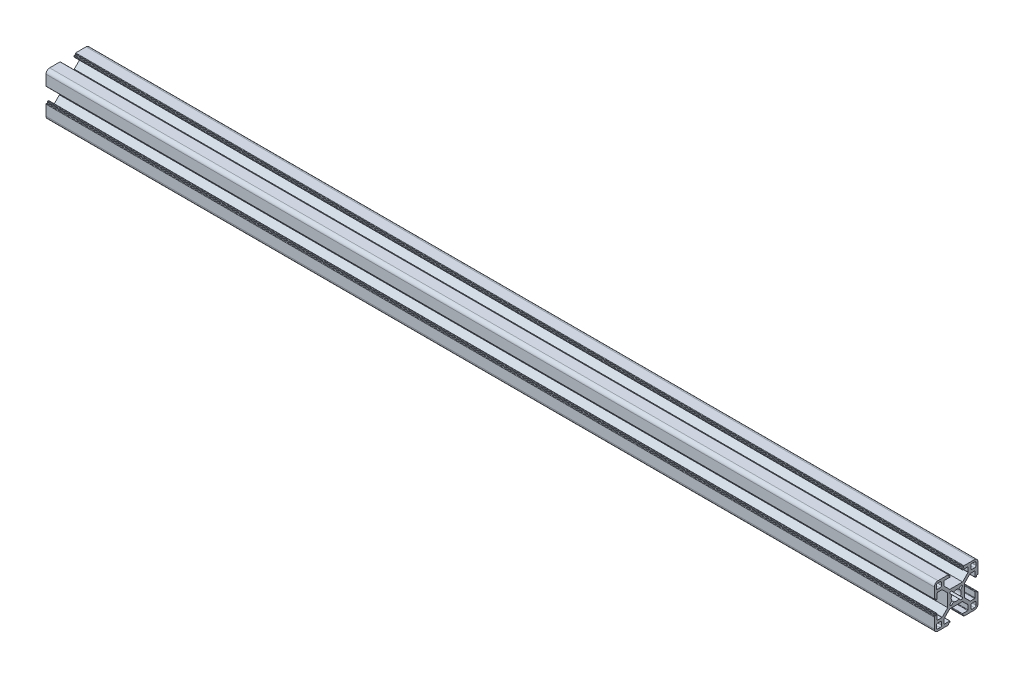
SolidWorks part; units mm, degrees
material "2.0572 (CuZn40Mn2Fe1)"
ref_plane "Front Plane" through (0, 0, 0) normal (0, 0, 1) x (1, 0, 0)
ref_plane "Top Plane" through (0, 0, 0) normal (0, 1, 0) x (1, 0, 0)
ref_plane "Right Plane" through (0, 0, 0) normal (1, 0, 0) x (0, 0, -1)
ref_axis "Axis_X" through (-58.3, 0, 0) along (1, 0, 0)
ref_axis "Axis_Y" through (0, 38.5, 0) along (0, -1, 0)
ref_axis "Axis_Z" through (0, 0, -4.5) along (0, 0, 1)
sketch "Sketch2" plane through (0, 0, 0) normal (1, 0, 0) x (0, 0, -1)
  line L1 (-15, 15) -> (15, 15)
  line L2 (-15, 15) -> (-15, -15)
  line L3 (-15, -15) -> (15, -15)
  line L4 (15, 15) -> (15, -15)
  line L5 (-15, 15) -> (15, -15) construction
  line L6 (-15, -15) -> (15, 15) construction
  point P0 (0, 0)
  dimension "D1" = 30
  dimension "D2" = 30
extrude "Boss-Extrude1" add sketch "Sketch2" along normal blind 610
sketch "Sketch5" plane through (610, 0, 0) normal (1, 0, 0) x (0, 0, -1)
  circle A0 centre (0, 0) radius 3.4
  dimension "D1" = 6.8
extrude "Cut-Extrude2" cut sketch "Sketch5" against normal through all
sketch "Sketch4" plane through (610, 0, 0) normal (1, 0, 0) x (0, 0, -1)
  line L0 (-4.3858, -5.8) -> (4.3858, -5.8)
  line L1 (4.3858, -5.8) -> (8.1621, -9.5763)
  line L2 (8.25, -9.7885) -> (8.25, -13)
  line L3 (8.25, -13) -> (4.1, -13)
  line L4 (4.1, -13) -> (4.1, -14)
  line L5 (4.1, -14) -> (5.1, -14)
  line L6 (5.1, -14) -> (5.1, -15)
  line L7 (-15, -15) -> (15, -15) construction
  line L8 (5.1, -15) -> (-5.1, -15)
  line L9 (-5.1, -15) -> (-5.1, -14)
  line L10 (-5.1, -14) -> (-4.1, -14)
  line L11 (-4.1, -14) -> (-4.1, -13)
  line L12 (-4.1, -13) -> (-8.25, -13)
  line L13 (-8.25, -13) -> (-8.25, -9.7885)
  line L14 (-8.1621, -9.5763) -> (-4.3858, -5.8)
  line L16 (-4.1, -13) -> (4.1, -13) construction
  line L17 (0, -14) -> (0, -15) construction
  line L18 (-4.1, -14) -> (4.1, -14) construction
  line L19 (0, -5.8) -> (0, -13) construction
  line L20 (0, -13) -> (0, -14) construction
  line L21 (15, -15) -> (15, 15) construction
  line L22 (11.05, -10.05) -> (12.65, -10.05)
  line L23 (10.05, -11.05) -> (10.05, -12.65)
  line L24 (11.05, -13.65) -> (12.65, -13.65)
  line L25 (13.65, -11.05) -> (13.65, -12.65)
  line L26 (10.05, -10.05) -> (13.65, -13.65) construction
  line L27 (10.05, -13.65) -> (13.65, -10.05) construction
  line L28 (0, 0) -> (3.5355, -3.5355) construction
  line L29 (15, -15) -> (15, 15) construction
  line L30 (4.0659, -3.0052) -> (2.8753, -1.8146)
  line L31 (3.0052, -4.0659) -> (1.8146, -2.8753)
  arc A0 (12.65, -13.65) -> (13.65, -12.65) centre (12.65, -12.65) ccw
  arc A1 (11.05, -13.65) -> (10.05, -12.65) centre (11.05, -12.65) cw
  arc A2 (10.05, -11.05) -> (11.05, -10.05) centre (11.05, -11.05) cw
  arc A3 (12.65, -10.05) -> (13.65, -11.05) centre (12.65, -11.05) cw
  arc A4 (3.0052, -4.0659) -> (4.0659, -3.0052) centre (3.5355, -3.5355) ccw
  circle A5 centre (0, 0) radius 3.4 construction
  arc A6 (1.8146, -2.8753) -> (2.8753, -1.8146) centre (0, 0) ccw
  arc A7 (-8.25, -9.7885) -> (-8.1621, -9.5763) centre (-7.95, -9.7885) cw
  arc A8 (8.25, -9.7885) -> (8.1621, -9.5763) centre (7.95, -9.7885) ccw
  point P18 (11.85, -11.85)
  point P47 (-8.25, -9.6642)
  point P55 (8.25, -9.6642)
  dimension "D11" = 1
  dimension "D14" = 1.5
  dimension "D2" = 0.3
  dimension "D1" = 9.2
  dimension "D3" = 1
  dimension "D4" = 8.2
  dimension "D5" = 10.2
  dimension "D6" = 16.5
  dimension "D7" = 2
  dimension "D8" = 1.35
  dimension "D9" = 1.35
  dimension "D10" = 3.6
  dimension "D12" = 45
  dimension "D13" = 5
  dimension "D15" = 5.4237
extrude "Cut-Extrude1" cut sketch "Sketch4" against normal through all
fillet "Fillet1" radius 2.5 1 edges at (305, -15, -15)
fillet "Fillet2" radius 0.3 10 edges at (305, -14, -5.1) (305, -15, -5.1) (305, -14, -4.1) (305, -13, -4.1) (305, -13, -8.25) (305, -13, 8.25) (305, -13, 4.1) (305, -14, 4.1) (305, -14, 5.1) (305, -15, 5.1)
pattern_circular "CirPattern1" count 4 over 360 about axis through (0, 0, 0) along (1, 0, 0) of "Cut-Extrude1", "Fillet1", "Fillet2"
equation "\"Factor\"= 1.082532"
